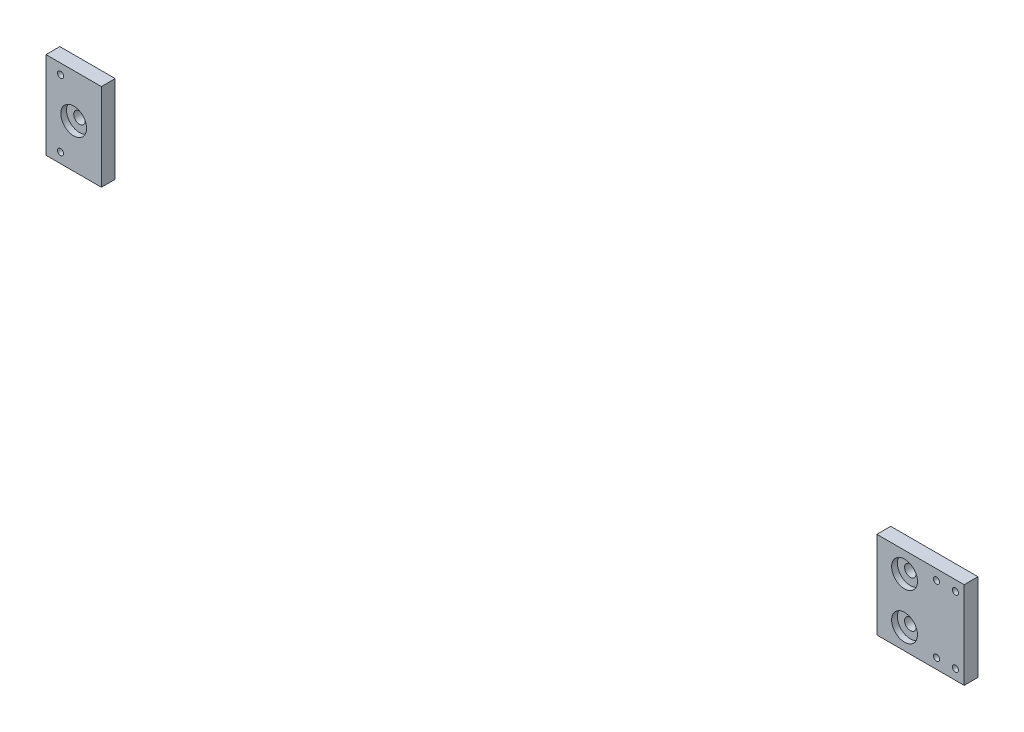
SolidWorks part; units mm, degrees
other "Rear Bracket"
other "Front Bracket"
ref_plane "Front Plane" through (0, 0, 0) normal (0, 0, 1) x (1, 0, 0)
ref_plane "Top Plane" through (0, 0, 0) normal (0, 1, 0) x (1, 0, 0)
ref_plane "Right Plane" through (0, 0, 0) normal (1, 0, 0) x (0, 0, -1)
sketch "Sketch2" plane through (-0.0002, 0, 0.001) normal (0, 0, 1) x (1, 0, 0)
  line L0 (304.7252, 30) -> (276.2371, 30)
  line L1 (-295.2748, -30) -> (-257.1748, -30)
  line L2 (-295.2748, -30) -> (-295.2748, 30)
  line L3 (-295.2748, 30) -> (-257.1748, 30)
  line L4 (-257.1748, -30) -> (-257.1748, 30)
  line L5 (-295.2748, -30) -> (-257.1748, 30) construction
  line L6 (-295.2748, 30) -> (-257.1748, -30) construction
  line L7 (304.7252, -30) -> (342.8252, -30)
  line L8 (304.7252, -30) -> (304.7252, 30) construction
  line L9 (304.7252, 30) -> (342.8252, 30)
  line L10 (342.8252, -30) -> (342.8252, 30)
  line L11 (304.7252, -30) -> (342.8252, 30) construction
  line L12 (304.7252, 30) -> (342.8252, -30) construction
  line L13 (276.2371, -152.388) -> (276.2371, 152.412) construction
  line L14 (276.2371, 30) -> (276.2371, -30)
  line L15 (276.2371, -30) -> (304.7252, -30)
  circle A0 centre (-276.2248, 0) radius 3.9688
  circle A1 centre (-276.2248, 0) radius 8.89
  circle A2 centre (323.7752, 0) radius 3.9688 construction
  circle A3 centre (323.7752, 0) radius 8.89 construction
  point P0 (-276.2248, 0)
  point P9 (323.7752, 0)
  dimension "D3" = 17.78
  dimension "D4" = 7.9375
  dimension "D1" = 38.1
  dimension "D2" = 60
  dimension "D6" = 600
  dimension "D5" = 2
extrude "Main Extrusion" add sketch "Sketch2" along normal blind 5.5575 contours L1 L4 L3 L2 A1 | A1 A0 | L7 L10 L9 L8 A3 | A3 A2 region at (309.531, 0, 0.001) region at (-294.5643, 0, 0.001) region at (-284.8636, 0, 0.001)
extrude "Counterbore extrusion" add sketch "Sketch2<3>" along normal blind 9.525 contours L1 L4 L3 L2 A1 | L7 L10 L9 L8 A3 region at (309.531, 0, 0.001) region at (-294.5643, 0, 0.001)
sketch "Sketch2<3>" plane through (-0.0002, 0, 0.001) normal (0, 0, 1) x (1, 0, 0) same geometry as "Sketch2"
sketch "Sketch3" plane through (0, 0, 9.526) normal (0, 0, 1) x (1, 0, 0)
  line L0 (-295.275, 0) -> (-257.175, 0) construction
  line L2 (-257.175, -30) -> (-257.175, 30) construction
  circle A0 centre (-285.275, 23) radius 2.1
  circle A1 centre (-285.275, -23) radius 2.1
  point P6 (-276.225, 0)
  dimension "D1" = 4.2
  dimension "D2" = 46
  dimension "D3" = 10
extrude "M5 Threaded holse for front bracket" cut sketch "Sketch3" against normal up to surface (9.525 mm away) up to face at (-272.2562, 0, 0.001)
sketch "Sketch5" plane through (0, 0, 9.526) normal (0, 0, 1) x (1, 0, 0)
  line L0 (317.275, 23) -> (330.275, 23) construction
  line L1 (317.275, 23) -> (317.275, -23) construction
  circle A0 centre (317.275, 23) radius 2.1
  circle A1 centre (330.275, 23) radius 2.1
  circle A2 centre (330.275, -23) radius 2.1
  circle A3 centre (317.275, -23) radius 2.1
  point P0 (323.775, 0)
  point P5 (323.775, 23)
  point P6 (317.275, 0)
  dimension "D6" = 4.2
  dimension "D3" = 90
  dimension "D4" = 13
  dimension "D5" = 46
  dimension "D1" = 2
  dimension "D2" = 2
extrude "M5 Threaded holes for bracket" cut sketch "Sketch5" against normal up to surface (9.525 mm away) up to face at (309.531, 0, 0.001)
sketch "Sketch6" plane through (0, 0, 9.526) normal (0, 0, 1) x (1, 0, 0)
  line L0 (295.275, -171.45) -> (295.275, 171.45) construction
  line L1 (295.275, -171.45) -> (295.275, 171.45) construction
  line L2 (13.75, 0) -> (-13.75, 0) construction
  circle A0 centre (295.275, 15.875) radius 8.89
  circle A1 centre (295.275, 15.875) radius 3.9688
  circle A2 centre (323.775, 0) radius 8.89 construction
  circle A3 centre (323.775, 0) radius 3.9688 construction
  circle A4 centre (295.275, -15.875) radius 3.9688
  circle A5 centre (295.275, -15.875) radius 8.89
  dimension "D1" = 31.75
extrude "centre bore" cut sketch "Sketch6" against normal through all contours L1 A1 | A1 L1 | L1 A4 | A4 L1 region at (293.5906, -15.875, 9.526) region at (296.9594, -15.875, 9.526) region at (293.5906, 15.875, 9.526) region at (296.9594, 15.875, 9.526)
extrude "counterbore" cut sketch "Sketch6<3>" against normal offset from surface (3.9675 mm away) 5.5575 up to face at (309.531, 0, 0.001)
sketch "Sketch6<3>" plane through (0, 0, 9.526) normal (0, 0, 1) x (1, 0, 0) same geometry as "Sketch6"
sketch "Sketch7" plane through (0, 0, 9.526) normal (0, 0, 1) x (1, 0, 0)
  line L1 (342.825, 30) -> (336.275, 30)
  line L2 (342.825, 30) -> (342.825, -30)
  line L3 (342.825, -30) -> (336.275, -30)
  line L4 (336.275, 30) -> (336.275, -30)
extrude "stupid cut" cut sketch "Sketch7" against normal through all
